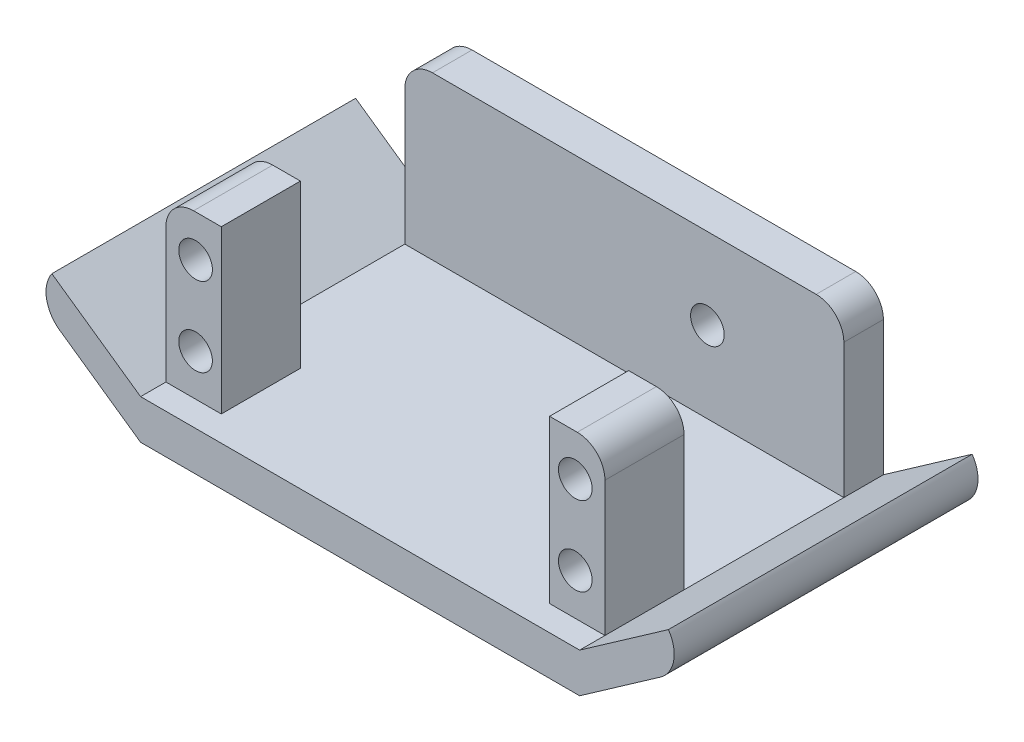
SolidWorks part; units mm, degrees
ref_plane "Front" through (0, 0, 0) normal (0, 0, 1) x (1, 0, 0)
ref_plane "Top" through (0, 0, 0) normal (0, 1, 0) x (1, 0, 0)
ref_plane "Right" through (0, 0, 0) normal (1, 0, 0) x (0, 0, -1)
sketch "Sketch1" plane through (0, 0, 0) normal (0, 1, 0) x (1, 0, 0)
  line L1 (0, 0) -> (55.5, 0)
  line L2 (0, 0) -> (0, 38.4)
  line L3 (0, 38.4) -> (55.5, 38.4)
  line L4 (55.5, 0) -> (55.5, 38.4)
  dimension "D1" = 55.5
  dimension "D2" = 38.4
extrude "base" add sketch "Sketch1" along normal blind 5
sketch "Sketch2" plane through (0, 0, -38.4) normal (0, 0, -1) x (-1, 0, 0)
  line L1 (0, 5) -> (0, 0) construction
  line L2 (-55.5, 0) -> (0, 0)
  line L3 (-55.5, 0) -> (-55.5, 25.5)
  line L4 (-55.5, 25.5) -> (0, 25.5)
  line L5 (0, 0) -> (0, 25.5)
  line L6 (-55.5, 5) -> (0, 5) construction
  dimension "D1" = 20.5
extrude "wall" add sketch "Sketch2" against normal blind 5
ref_plane "Plane1" through (0, 0, -8.2) normal (0, 0, 1) x (1, 0, 0)
sketch "Sketch3" plane through (0, 0, -8.2) normal (0, 0, 1) x (1, 0, 0)
  line L0 (0, 5) -> (55.5, 5) construction
  line L1 (0, 25.5) -> (7, 25.5)
  line L2 (0, 25.5) -> (0, 5)
  line L3 (0, 5) -> (7, 5)
  line L4 (7, 25.5) -> (7, 5)
  line L5 (27.75, 5) -> (27.75, 25.5) construction
  line L6 (55.5, 5) -> (0, 5) construction
  line L7 (0, 25.5) -> (55.5, 25.5) construction
  line L8 (55.5, 5) -> (48.5, 5)
  line L9 (48.5, 25.5) -> (48.5, 5)
  line L10 (55.5, 25.5) -> (48.5, 25.5)
  line L11 (55.5, 25.5) -> (55.5, 5)
  dimension "D1" = 7
extrude "mountingTabs" add sketch "Sketch3" along normal blind 5
sketch "Sketch4" plane through (0, 0, 0) normal (0, 0, 1) x (1, 0, 0)
  line L0 (27.75, 0) -> (27.75, 25.5) construction
  line L1 (0, 0) -> (55.5, 0) construction
  line L2 (0, 25.5) -> (55.5, 25.5) construction
  line L3 (0, 0) -> (-10.2089, 7.1483)
  line L4 (0, 5) -> (-11.2182, 12.8551)
  line L5 (0, 5) -> (0, 0)
  line L6 (55.5, 5) -> (66.7182, 12.8551)
  line L7 (55.5, 5) -> (55.5, 0)
  line L8 (55.5, 0) -> (65.7089, 7.1483)
  arc A0 (-11.2182, 12.8551) -> (-10.2089, 7.1483) centre (-7.8572, 10.5069) ccw
  arc A1 (66.7182, 12.8551) -> (65.7089, 7.1483) centre (63.3572, 10.5069) cw
  dimension "D1" = 145
  dimension "D2" = 12.4627
  dimension "D3" = 13.6949
extrude "lips" add sketch "Sketch4" against normal up to surface (38.4 mm away) up to face at (27.75, 12.75, -38.4)
sketch "Sketch5" plane through (0, 0, -3.2) normal (0, 0, 1) x (1, 0, 0)
  line L0 (27.75, 0) -> (27.75, 25.5) construction
  line L3 (0, 15.25) -> (55.5, 15.25) construction
  line L4 (0, 25.5) -> (0, 5) construction
  line L5 (55.5, 5) -> (55.5, 25.5) construction
  line L6 (7, 25.5) -> (0, 25.5) construction
  line L7 (0, 0) -> (55.5, 0) construction
  line L8 (0, 25.5) -> (55.5, 25.5) construction
  circle A0 centre (3.75, 20.25) radius 2.125
  circle A1 centre (3.75, 10.25) radius 2.125
  circle A4 centre (51.75, 10.25) radius 2.125
  circle A5 centre (51.75, 20.25) radius 2.125
  dimension "D1" = 4.25
  dimension "D2" = 5.25
  dimension "D3" = 3.75
extrude "mountingHoles" cut sketch "Sketch5" against normal blind 5
fillet "fillets" radius 3.5 4 edges at (55.5, 25.5, -35.9) (55.5, 25.5, -5.7) (0, 25.5, -35.9) (0, 25.5, -5.7)
sketch "Sketch6" plane through (0, 0, -33.4) normal (0, 0, 1) x (1, 0, 0)
  line L0 (3.5, 25.5) -> (52, 25.5) construction
  line L1 (55.5, 5) -> (55.5, 22) construction
  circle A0 centre (38.25, 15.25) radius 2.125
  dimension "D1" = 4.25
  dimension "D2" = 10.25
  dimension "D3" = 17.25
extrude "throughHole" cut sketch "Sketch6" against normal blind 5
sketch "Sketch7" plane through (0, 0, -8.2) normal (0, 0, -1) x (-1, 0, 0)
  line L4 (-48.5, 25.5) -> (-52, 25.5)
  line L5 (-55.5, 22) -> (-55.5, 5)
  line L6 (-55.5, 5) -> (-48.5, 5)
  line L7 (-48.5, 5) -> (-48.5, 25.5)
  line L8 (-48.5, 25.5) -> (-52, 25.5)
  line L9 (-55.5, 22) -> (-55.5, 5)
  line L10 (-55.5, 5) -> (-48.5, 5)
  line L11 (-48.5, 5) -> (-48.5, 25.5)
  line L12 (0, 5) -> (0, 22)
  line L13 (-3.5, 25.5) -> (-7, 25.5)
  line L14 (-7, 25.5) -> (-7, 5)
  line L15 (-7, 5) -> (0, 5)
  line L16 (0, 5) -> (0, 22)
  line L17 (-3.5, 25.5) -> (-7, 25.5)
  line L18 (-7, 25.5) -> (-7, 5)
  line L19 (-7, 5) -> (0, 5)
  circle A0 centre (-51.75, 20.25) radius 2.125 construction
  arc A1 (-52, 25.5) -> (-55.5, 22) centre (-52, 22) ccw
  arc A2 (-52, 25.5) -> (-55.5, 22) centre (-52, 22) ccw
  arc A3 (0, 22) -> (-3.5, 25.5) centre (-3.5, 22) ccw
  arc A4 (0, 22) -> (-3.5, 25.5) centre (-3.5, 22) ccw
  circle A5 centre (-51.75, 20.25) radius 2.125
  circle A6 centre (-51.75, 10.25) radius 2.125 construction
  circle A7 centre (-51.75, 10.25) radius 2.125
  circle A8 centre (-3.75, 10.25) radius 2.125 construction
  circle A9 centre (-3.75, 10.25) radius 2.125
  circle A10 centre (-3.75, 20.25) radius 2.125 construction
  circle A11 centre (-3.75, 20.25) radius 2.125
  dimension "D1" = 0
  dimension "D2" = 0
extrude "Boss-Extrude1" add sketch "Sketch7" along normal blind 5
